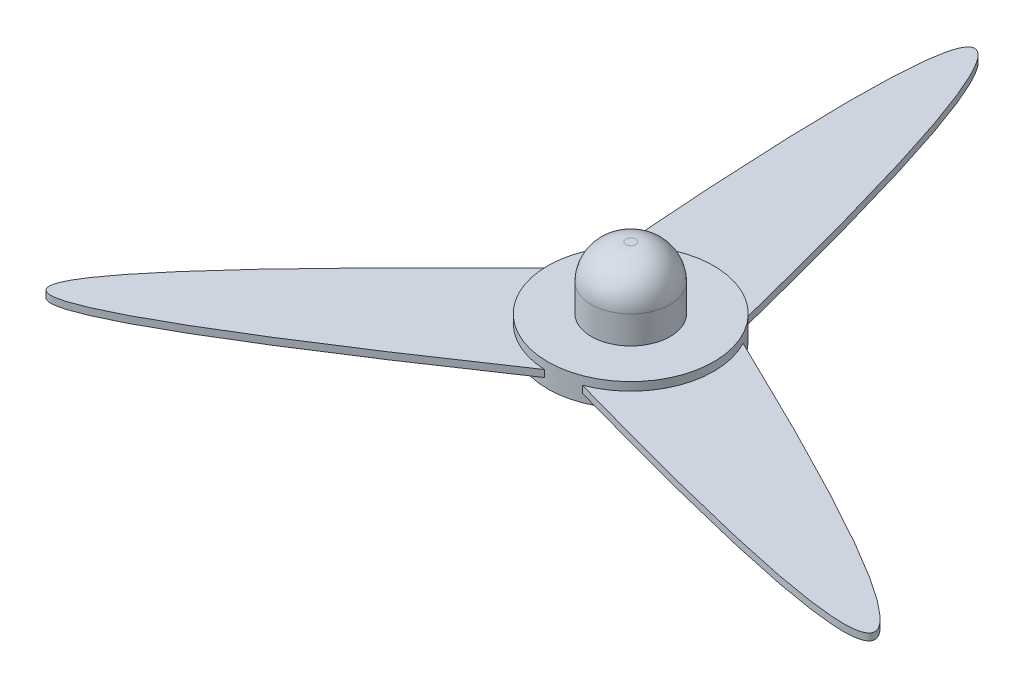
SolidWorks part; units mm, degrees
material "ABS"
ref_plane "Front Plane" through (0, 0, 0) normal (0, 0, 1) x (1, 0, 0)
ref_plane "Top Plane" through (0, 0, 0) normal (0, 1, 0) x (1, 0, 0)
ref_plane "Right Plane" through (0, 0, 0) normal (1, 0, 0) x (0, 0, -1)
sketch "Sketch1" plane through (0, 0, 0) normal (0, 1, 0) x (1, 0, 0)
  line L0 (0, 0) -> (-232.1844, -189.9747) construction
  arc A0 (-50.8165, 31.9011) -> (-59.2113, 9.6964) centre (0, 0) ccw
  arc A1 (53.0354, 28.0579) -> (38.003, 46.4303) centre (0, 0) ccw
  arc A2 (-2.2189, -59.959) -> (21.2084, -56.1267) centre (0, 0) ccw
  circle A3 centre (0, 0) radius 300 construction
  circle A4 centre (0, 0) radius 60 construction
  spline S0 degree 2 poles (-50.8165, 31.9011) (-90.4547, 552.9642) (38.003, 46.4303) knots 0 0 0 1 1 1
  spline S1 degree 2 poles (53.0354, 28.0579) (524.1084, -198.146) (21.2084, -56.1267) knots 0 0 0 1 1 1
  spline S2 degree 2 poles (-2.2189, -59.959) (-433.6537, -354.8182) (-59.2113, 9.6964) knots 0 0 0 1 1 1
  point P17 (0, 0)
  dimension "D1" = 600
  dimension "D3" = 120
  dimension "D2" = 90
  dimension "D4" = 300
extrude "Boss-Extrude1" add sketch "Sketch1" along normal blind 2.5 and the other way blind 2.5 contours S0 A1 S1 A2 S2 A0
sketch "Sketch3" plane through (0, 2.5, 0) normal (0, 1, 0) x (1, 0, 0)
  circle A0 centre (0, 0) radius 60
extrude "Boss-Extrude2" add sketch "Sketch3" along normal blind 6 and the other way blind 11
sketch "Sketch4" plane through (0, 8.5, 0) normal (0, 1, 0) x (1, 0, 0)
  circle A0 centre (0, 0) radius 28.5
  dimension "D1" = 57
sketch "Sketch5" plane through (0, -8.5, 0) normal (0, -1, 0) x (1, 0, 0)
  circle A0 centre (0, 0) radius 24
  dimension "D1" = 48
extrude "Boss-Extrude5" add sketch "Sketch4" along normal blind 45 contours A0
fillet "Fillet4" radius 25 1 edges at (0, 53.5, 28.5) type face fillet first side face at (0, 53.5, 28.5) second side face at (0, 53.5, 28.5)
extrude "Cut-Extrude2" cut sketch "Sketch5" against normal blind 37 contours A0
